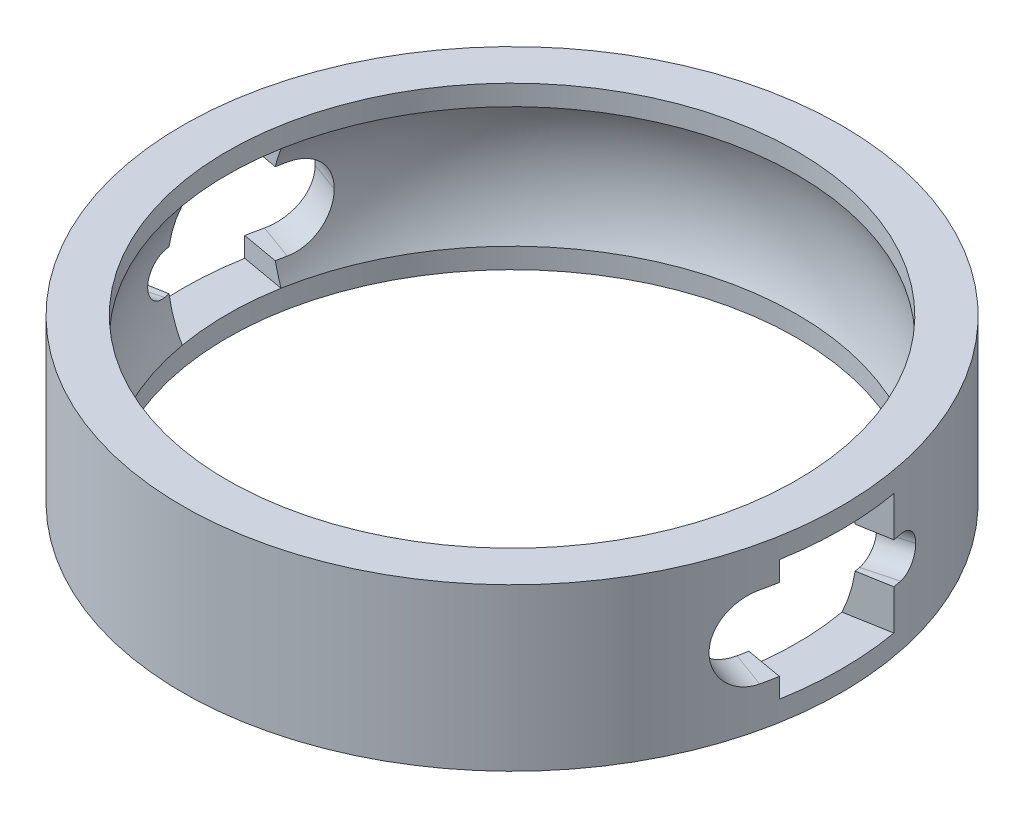
SolidWorks part; units mm, degrees
material "Nylon 101"
ref_plane "Front Plane" through (0, 0, 0) normal (0, 0, 1) x (1, 0, 0)
ref_plane "Top Plane" through (0, 0, 0) normal (0, 1, 0) x (1, 0, 0)
ref_plane "Right Plane" through (0, 0, 0) normal (1, 0, 0) x (0, 0, -1)
sketch "Sketch1" plane through (0, 0, 0) normal (0, 0, 1) x (1, 0, 0)
  line L0 (0, 0) -> (0, 12.3745) construction
  line L1 (-17.78, 0) -> (0, 0) construction
  line L2 (-20.574, 5.0419) -> (-17.78, 5.0419)
  line L3 (-20.574, 5.0419) -> (-20.574, -5.0419)
  line L4 (-20.574, -5.0419) -> (-17.78, -5.0419)
  line L5 (-17.78, 5.0419) -> (-17.78, -5.0419)
  dimension "D1" = 35.56
  dimension "D2" = 2.794
  dimension "D3" = 10.0838
revolve "Revolve1" add sketch "Sketch1" angle 360 about L0
sketch "Sketch2" plane through (0, 0, 0) normal (0, 0, 1) x (1, 0, 0)
  line L0 (-17.78, 5.0419) -> (-17.78, -5.0419) construction
  line L1 (-17.78, 0) -> (-18.5737, 0) construction
  line L2 (-17.78, 3.7719) -> (-15.24, 3.7719)
  line L3 (-15.24, 3.7719) -> (-15.24, -3.7719)
  line L4 (-15.24, -3.7719) -> (-17.78, -3.7719)
  line L5 (-17.78, 3.7719) -> (-17.78, 5.0419) construction
  arc A0 (-17.78, 3.7719) -> (-17.78, -3.7719) centre (-9.2148, 0) ccw
  dimension "D1" = 0.7937
  dimension "D2" = 1.27
  dimension "D3" = 2.54
revolve "Cut-Revolve1" cut sketch "Sketch2" angle 360 about L0
sketch "Sketch4" plane through (0, 0, 0) normal (0, 0, 1) x (1, 0, 0)
  line L1 (-1.27, 3.7592) -> (-1.27, -3.7592)
  line L2 (-1.27, 3.7592) -> (0, 3.7592)
  line L3 (0, 3.7592) -> (0, -3.7592) construction
  line L4 (0, -3.7592) -> (-1.27, -3.7592)
  arc A0 (0, -3.7592) -> (0, 3.7592) centre (0, 0) ccw
  dimension "D2" = 7.5184
  dimension "D1" = 1.27
extrude "Cut-Extrude1" [suppressed] cut sketch "Sketch4" against normal through all
sketch "Sketch5" [suppressed] plane through (0, 0, 0) normal (0, 1, 0) x (1, 0, 0)
  line L0 (0, 0) -> (0, 20.574) construction
  line L1 (0, 0) -> (20.574, 0) construction
  line L2 (0, 0) -> (7.0367, -19.3332) construction
  line L3 (12.5813, -17.3152) -> (1.4922, -21.3513) construction
  circle A0 centre (0, 0) radius 20.574 construction
  dimension "D1" = 160
ref_plane "Plane1" [suppressed] through (7.0367, 0, 19.3332) normal (0.342, 0, 0.9397) x (0.9397, 0, -0.342)
sketch "Sketch6" [suppressed] plane through (7.0367, 0, 19.3332) normal (0.342, 0, 0.9397) x (0.9397, 0, -0.342)
  line L0 (1.27, 3.7592) -> (0, 3.7592)
  line L1 (1.27, 3.7592) -> (1.27, 1.2531)
  line L2 (1.27, -1.2531) -> (1.27, -3.7592)
  line L3 (0, 3.7592) -> (0, -3.7592)
  line L4 (0, -3.7592) -> (1.27, -3.7592)
  line L5 (1.27, 0) -> (0, 0) construction
  arc A0 (1.27, 1.2531) -> (1.27, -1.2531) centre (1.27, 0) cw
  point P11 (0, 0)
  dimension "D3" = 1.2531
  dimension "D1" = 1.27
  dimension "D2" = 7.5184
extrude "Cut-Extrude2" [suppressed] cut sketch "Sketch6" against normal up to surface (2.1282 mm away)
pattern_circular "CirPattern1" [suppressed] count 2 over 360 of bodies 104
sketch "Sketch7" plane through (0, 0, 0) normal (0, 0, 1) x (1, 0, 0)
  line L1 (-27.94, 3.7719) -> (-17.78, 3.7719)
  line L2 (-27.94, 3.7719) -> (-27.94, -3.7719)
  line L3 (-27.94, -3.7719) -> (-17.78, -3.7719)
  line L4 (-17.78, 3.7719) -> (-17.78, -3.7719)
  line L8 (0, 0) -> (0, 11.6555) construction
  dimension "D1" = 10.16
revolve "Cut-Revolve2" cut sketch "Sketch7" angle 20 mid plane about L8
sketch "Sketch8" plane through (0, 0, 0) normal (-0.1736, 0, 0.9848) x (0.9848, 0, 0.1736)
  line L0 (-18.2225, 0) -> (0, 0) construction
  line L1 (-28.3825, 2.54) -> (-18.2225, 2.54)
  line L2 (-28.3825, 2.54) -> (-28.3825, -2.54)
  line L3 (-28.3825, -2.54) -> (-18.2225, -2.54)
  line L4 (-18.2225, 2.54) -> (-18.2225, -2.54)
  line L5 (0, 0) -> (0, 12.0795) construction
  arc A0 (-17.78, 3.7719) -> (-17.78, -3.7719) centre (-9.2148, 0) ccw construction
  dimension "D1" = 5.08
  dimension "D2" = 10.16
revolve "Cut-Revolve3" cut sketch "Sketch8" angle 10 about L5 reverse direction yes
sketch "Sketch9" plane through (0, 0, 0) normal (-0.1736, 0, -0.9848) x (-0.9848, 0, 0.1736)
  line L0 (18.4872, 0) -> (0, 0) construction
  line L1 (18.4872, 1.27) -> (28.6472, 1.27)
  line L2 (18.4872, 1.27) -> (18.4872, -1.27)
  line L3 (18.4872, -1.27) -> (28.6472, -1.27)
  line L4 (28.6472, 1.27) -> (28.6472, -1.27)
  line L5 (0, 0) -> (0, 12.4005) construction
  arc A0 (17.78, -3.7719) -> (17.78, 3.7719) centre (9.2148, 0) ccw construction
  dimension "D1" = 2.54
  dimension "D2" = 10.16
revolve "Cut-Revolve4" cut sketch "Sketch9" angle 5 about L5
pattern_circular "CirPattern2" count 2 over 360 about axis through (0, 0, 0) along (0, -1, 0) of "Cut-Revolve2", "Cut-Revolve3", "Cut-Revolve4"
fillet "Fillet1" radius 2.54 4 edges at (18.2284, 2.54, 6.6346) (18.2284, -2.54, 6.6346) (-18.2284, -2.54, -6.6346) (-18.2284, 2.54, -6.6346)
fillet "Fillet2" radius 1.27 4 edges at (-18.8651, -1.27, 5.0549) (-18.8651, 1.27, 5.0549) (18.8651, -1.27, -5.0549) (18.8651, 1.27, -5.0549)
equation "\"D3@Sketch6\"=\"D2@Sketch6\"/2/3"
